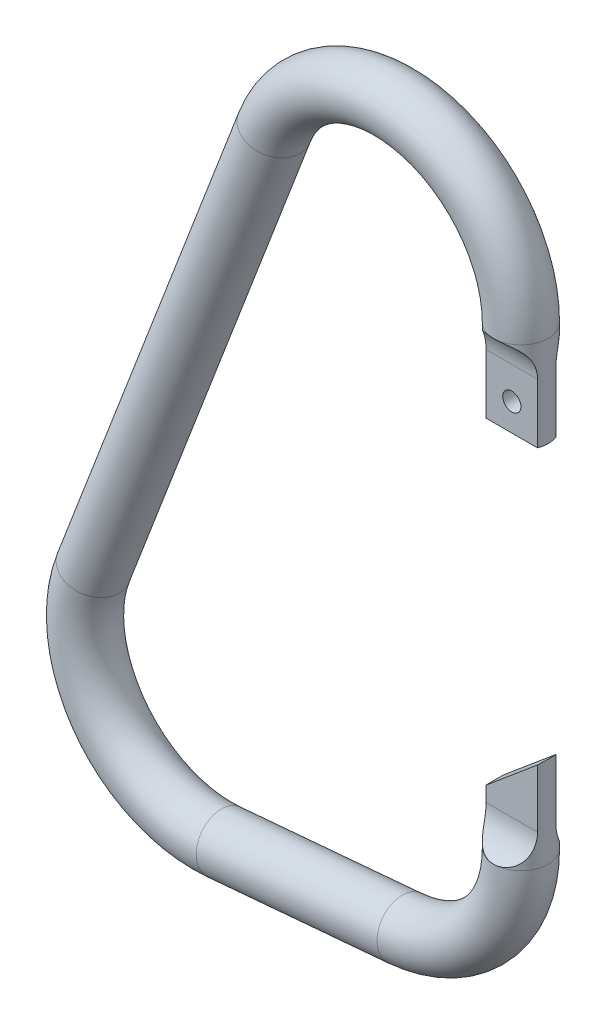
SolidWorks part; units mm, degrees
ref_plane "Front Plane" through (0, 0, 0) normal (0, 0, 1) x (1, 0, 0)
ref_plane "Top Plane" through (0, 0, 0) normal (0, 1, 0) x (1, 0, 0)
ref_plane "Right Plane" through (0, 0, 0) normal (1, 0, 0) x (0, 0, -1)
sketch "Sketch2" plane through (0, 0, 0) normal (0, 0, 1) x (1, 0, 0)
  line L0 (0, 0) -> (0, 5)
  line L1 (-13.5351, 7.5086) -> (-23.4652, -18.3602)
  line L2 (-16.32, -27.8421) -> (-6.3899, -26.9734)
  line L3 (0, -20) -> (0, -15)
  line L4 (-7, 5) -> (-7, -20) construction
  line L5 (-7, -20) -> (-16.9301, -20.8688) construction
  arc A0 (0, 5) -> (-13.5351, 7.5086) centre (-7, 5) ccw
  arc A1 (-23.4652, -18.3602) -> (-16.32, -27.8421) centre (-16.9301, -20.8688) ccw
  arc A2 (-6.3899, -26.9734) -> (0, -20) centre (-7, -20) ccw
  point P11 (-0.9928, -15)
  dimension "D2" = 7
  dimension "D3" = 7
  dimension "D1" = 95
  dimension "D4" = 21
  dimension "D5" = 5
  dimension "D6" = 5
  dimension "D7" = 15
sweep "Sweep1" add path "Sketch2" circular profile diameter 3 parameters "D3"=3
sketch "Sketch7" plane through (0, 0, 0) normal (0, 0, 1) x (1, 0, 0)
  line L0 (1.5, -15) -> (-3.267, -19)
  line L1 (-3.267, -19) -> (-3.267, -15)
  line L2 (-3.267, -15) -> (1.5, -15)
  circle A0 centre (0, 1.5) radius 0.5
  dimension "D3" = 1
  dimension "D1" = 40
  dimension "D2" = 4
  dimension "D4" = 1.5
extrude "Cut-Extrude1" cut sketch "Sketch7" against normal through all both and the other way through all
sketch "Sketch9" plane through (0, 0, 0) normal (1, 0, 0) x (0, 0, -1)
  line L1 (0.5, 0) -> (0.5, 3.2679)
  line L4 (0, -21.1796) -> (0, -13.9183) construction
  line L8 (0.5, -15) -> (0.5, -18.2679)
  line L15 (1.5, 5) -> (1.5, 0)
  line L16 (1.5, 0) -> (0.5, 0)
  line L17 (0.5, -15) -> (1.5, -15)
  line L18 (1.5, -15) -> (1.5, -20)
  arc A0 (0.5, 3.2679) -> (1.5, 5) centre (2.5, 3.2679) cw
  arc A3 (0.5, -18.2679) -> (1.5, -20) centre (2.5, -18.2679) ccw
  ellipse E0 centre (0, -16.2586) end of major axis (-1.5, -16.2586) minor radius 1.2586 construction
  point P0 (0.3519, -18.0934)
  point P31 (0, -15)
  dimension "D1" = 2
  dimension "D3" = 5
  dimension "D5" = 2
  dimension "D2" = 0.5
extrude "Cut-Extrude10" cut sketch "Sketch9" against normal blind 2 and the other way blind 2
mirror "Mirror1" about plane through (0, 0, 0) normal (0, 0, 1) of "Cut-Extrude10"
